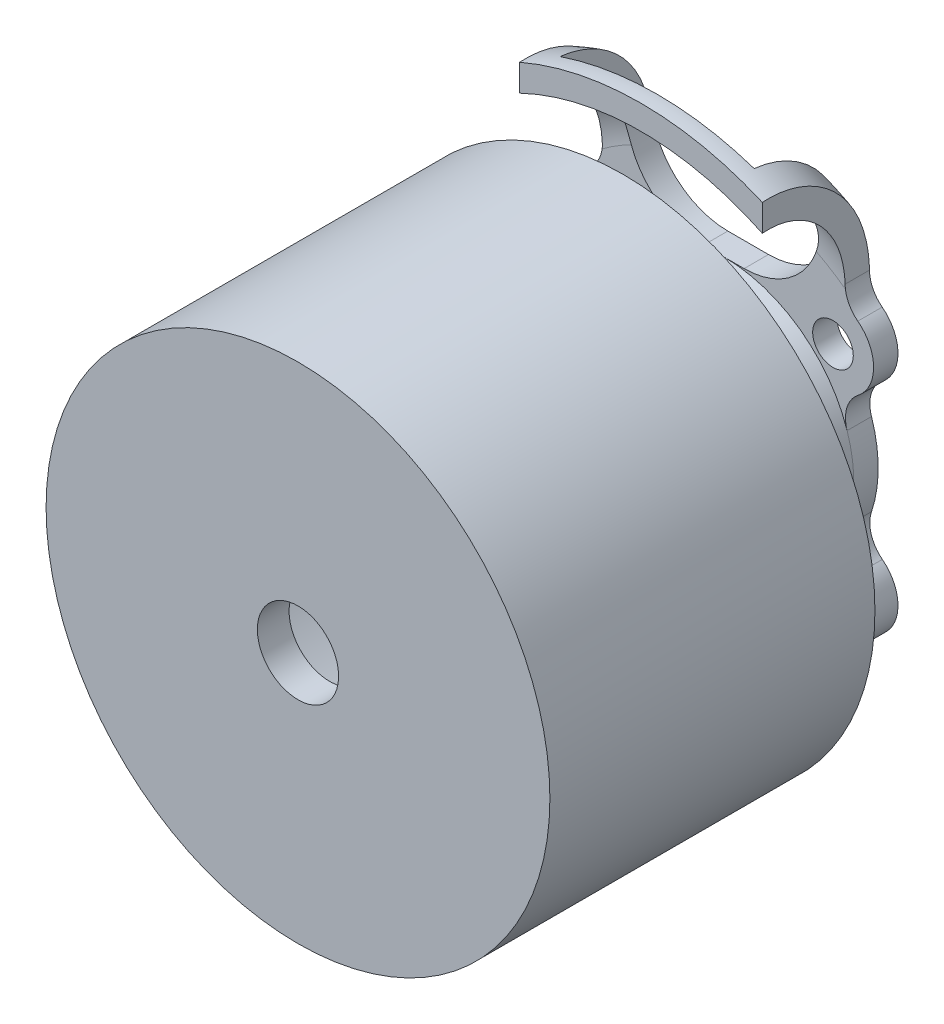
SolidWorks part; units mm, degrees
material "AISI 1020 Steel, Cold Rolled"
ref_plane "Front Plane" through (0, 0, 0) normal (0, 0, 1) x (1, 0, 0)
ref_plane "Top Plane" through (0, 0, 0) normal (0, 1, 0) x (1, 0, 0)
ref_plane "Right Plane" through (0, 0, 0) normal (1, 0, 0) x (0, 0, -1)
sketch "Sketch1" plane through (0, 0, 0) normal (1, 0, 0) x (0, 0, -1)
  line L1 (0, 15.5) -> (20, 15.5)
  line L3 (20, 0) -> (0, 0) construction
  line L4 (20, 2.5) -> (0, 2.5) construction
  line L5 (0, 15.5) -> (0, 2.5)
  line L6 (0, 2.5) -> (1.95, 2.5)
  line L7 (1.95, 2.5) -> (1.95, 13.5)
  line L8 (1.95, 13.5) -> (18.05, 13.5)
  line L9 (18.05, 13.5) -> (18.05, 2.5)
  line L10 (18.05, 2.5) -> (20, 2.5)
  line L11 (20, 6.5) -> (20, 15.5)
  line L12 (20, 2.5) -> (27.7, 2.5)
  line L13 (27.7, 2.5) -> (27.7, 12.5)
  line L14 (27.7, 18.75) -> (-25.5, 18.75) construction
  line L18 (20, 6.5) -> (26.2, 8)
  line L19 (26.2, 8) -> (26.2, 12.5)
  line L20 (21.1007, 18.7402) -> (21.1007, 17.2402)
  line L21 (26.2, 8) -> (27.7, 8) construction
  line L22 (10, 13.5) -> (10, 15.5) construction
  arc A2 (27.7, 12.5) -> (21.1007, 18.7402) centre (21.45, 12.5) ccw
  arc A3 (26.2, 12.5) -> (21.1007, 17.2402) centre (21.4471, 12.5) ccw
  dimension "D10" = 1.5
  dimension "D1" = 20
  dimension "D2" = 15.5
  dimension "D3" = 2.5
  dimension "D4" = 12.5
  dimension "D5" = 27.7
  dimension "D6" = 18.75
  dimension "D7" = 53.2
  dimension "D8" = 6.5
  dimension "D9" = 8
  dimension "D11" = 16.1
  dimension "D12" = 11
revolve "Revolve1" add sketch "Sketch1" angle 360 about L3
sketch "Sketch2" plane through (0, 0, -27.7) normal (0, 0, -1) x (-1, 0, 0)
  line L0 (-5.9675, 23.4161) -> (-5.9675, 12.7175)
  line L1 (-6.7175, -6.7175) -> (6.7175, -6.7175) construction
  line L2 (-6.7175, -6.7175) -> (-6.7175, 6.7175) construction
  line L3 (-6.7175, 6.7175) -> (6.7175, 6.7175) construction
  line L4 (6.7175, -6.7175) -> (6.7175, 6.7175) construction
  line L5 (-6.7175, -6.7175) -> (6.7175, 6.7175) construction
  line L6 (-6.7175, 6.7175) -> (6.7175, -6.7175) construction
  line L7 (-5.9675, 23.4161) -> (5.9675, 23.4161)
  line L8 (5.9675, 23.4161) -> (5.9675, 12.7175)
  line L9 (0, 0) -> (0, 23.4161) construction
  line L10 (1.25, 8) -> (-1.25, 8)
  line L11 (-7.4675, 23.4161) -> (-7.4675, 10.2795)
  line L12 (7.4675, 23.4161) -> (7.4675, 10.2795)
  line L13 (7.4675, 23.4161) -> (5.9675, 23.4161) construction
  line L14 (6.7175, 6.7175) -> (6.7175, 23.4161) construction
  line L15 (-5.9675, 23.4161) -> (-7.4675, 23.4161) construction
  circle A0 centre (0, 0) radius 9.5 construction
  circle A1 centre (0, 0) radius 8 construction
  circle A2 centre (0, 0) radius 12.5 construction
  circle A3 centre (-6.7175, 6.7175) radius 1.25
  circle A4 centre (6.7175, 6.7175) radius 1.25
  circle A5 centre (6.7175, -6.7175) radius 1.25
  circle A6 centre (-6.7175, -6.7175) radius 1.25
  circle A7 centre (6.7175, 6.7175) radius 2.5 construction
  circle A8 centre (6.7175, -6.7175) radius 2.5 construction
  circle A9 centre (-6.7175, -6.7175) radius 2.5 construction
  circle A11 centre (-6.7175, 6.7175) radius 2.5 construction
  arc A17 (-5.9675, 12.7175) -> (-1.25, 8) centre (-1.25, 12.7175) ccw
  arc A19 (5.9675, 12.7175) -> (1.25, 8) centre (1.25, 12.7175) cw
  arc A22 (-7.4675, 23.4161) -> (7.4675, 23.4161) centre (0, -0.8704) ccw
  arc A25 (8.2453, 8.6964) -> (8.2548, 4.746) centre (6.7175, 6.7175) cw
  arc A26 (7.5877, 2.5351) -> (7.5877, -2.5351) centre (0, 0) cw
  arc A27 (8.2548, -4.746) -> (4.746, -8.2548) centre (6.7175, -6.7175) cw
  arc A28 (2.5351, -7.5877) -> (-2.5351, -7.5877) centre (0, 0) cw
  arc A29 (-4.746, -8.2548) -> (-8.2548, -4.746) centre (-6.7175, -6.7175) cw
  arc A30 (-8.2453, 8.6964) -> (-8.2548, 4.746) centre (-6.7175, 6.7175) ccw
  arc A31 (-7.5877, 2.5351) -> (-7.5877, -2.5351) centre (0, 0) ccw
  arc A32 (-8.2453, 8.6964) -> (-7.4675, 10.2795) centre (-9.4675, 10.2795) ccw
  arc A33 (-7.5877, 2.5351) -> (-8.2548, 4.746) centre (-9.4846, 3.1689) ccw
  arc A34 (-8.2548, -4.746) -> (-7.5877, -2.5351) centre (-9.4846, -3.1689) ccw
  arc A35 (-4.746, -8.2548) -> (-2.5351, -7.5877) centre (-3.1689, -9.4846) cw
  arc A36 (2.5351, -7.5877) -> (4.746, -8.2548) centre (3.1689, -9.4846) cw
  arc A37 (8.2548, -4.746) -> (7.5877, -2.5351) centre (9.4846, -3.1689) cw
  arc A38 (7.5877, 2.5351) -> (8.2548, 4.746) centre (9.4846, 3.1689) cw
  arc A39 (8.2453, 8.6964) -> (7.4675, 10.2795) centre (9.4675, 10.2795) cw
  point P47 (7.4675, 9.1024)
  point P48 (-7.4675, 9.1024)
  point P50 (-7.4675, 9.1024)
  point P53 (-6.7972, 4.2188)
  point P56 (-6.7972, -4.2188)
  point P59 (-4.2188, -6.7972)
  point P62 (4.2188, -6.7972)
  point P65 (6.7972, -4.2188)
  point P68 (6.7972, 4.2188)
  point P71 (7.4675, 9.1024)
  dimension "D1" = 19
  dimension "D2" = 16
  dimension "D3" = 25
  dimension "D4" = 2.5
  dimension "D5" = 5
  dimension "D7" = 2
  dimension "D6" = 1.5
  dimension "D8" = 2.5
extrude "Cut-Extrude1" cut sketch "Sketch2" against normal offset from surface (5.5993 mm away) 1 up to face at (-17.2402, 0, -21.1007)
sketch "Sketch3" plane through (0, 0, -21.1007) normal (0, 0, 1) x (1, 0, 0)
  line L0 (-7.4675, 17.1988) -> (-7.4675, 0) construction
  line L1 (-7.4675, 0) -> (7.4675, 0) construction
  line L2 (7.4675, 0) -> (7.4675, 17.1988) construction
  line L4 (7.4675, 15.503) -> (7.4675, 17.1618) construction
  line L5 (7.4675, 17.1988) -> (7.4675, 15.503)
  line L6 (-7.4675, 17.1988) -> (-7.4675, 15.503)
  arc A0 (7.4675, 17.1988) -> (-7.4675, 17.1988) centre (0, 0) cw
  arc A1 (-7.4675, 15.503) -> (7.4675, 15.503) centre (0, 0) ccw
  arc A2 (5.9675, 16.1398) -> (-5.9675, 16.1398) centre (0, 0) ccw construction
  point P5 (0, 0)
  dimension "D1" = 18.75
extrude "Cut-Extrude2" cut sketch "Sketch3" against normal up to next
